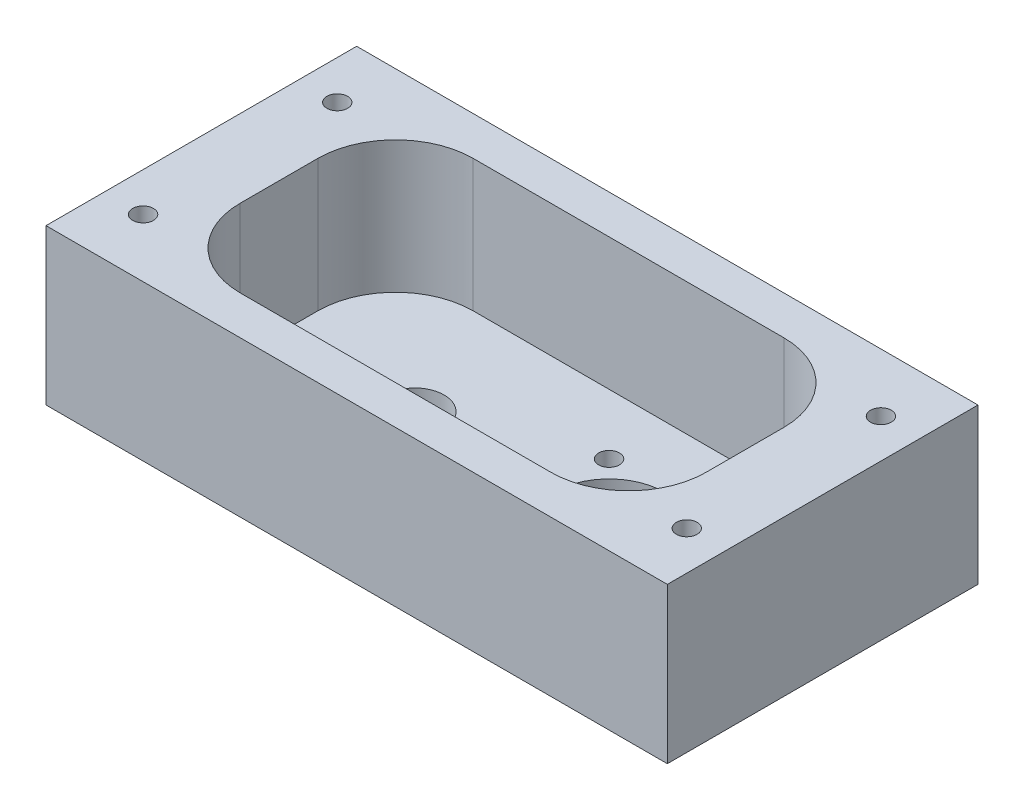
SolidWorks part; units mm, degrees
material "6061 Alloy"
ref_plane "Front Plane" through (0, 0, 0) normal (0, 0, 1) x (1, 0, 0)
ref_plane "Top Plane" through (0, 0, 0) normal (0, 1, 0) x (1, 0, 0)
ref_plane "Right Plane" through (0, 0, 0) normal (1, 0, 0) x (0, 0, -1)
sketch "Sketch1" plane through (0, 0, 0) normal (0, 1, 0) x (1, 0, 0)
  line L1 (-50.8, -25.4) -> (50.8, -25.4)
  line L2 (-50.8, -25.4) -> (-50.8, 25.4)
  line L3 (-50.8, 25.4) -> (50.8, 25.4)
  line L4 (50.8, -25.4) -> (50.8, 25.4)
  line L5 (-50.8, -25.4) -> (50.8, 25.4) construction
  line L6 (-50.8, 25.4) -> (50.8, -25.4) construction
  point P0 (0, 0)
  dimension "D1" = 101.6
  dimension "D2" = 50.8
extrude "Boss-Extrude1" add sketch "Sketch1" along normal blind 25.4
sketch "Sketch2" plane through (0, 0, 0) normal (0, -1, 0) x (1, 0, 0)
  line L0 (-50.8, 0) -> (50.8, 0) construction
  line L1 (-50.8, -25.4) -> (-50.8, 25.4) construction
  line L2 (50.8, 25.4) -> (50.8, -25.4) construction
  line L3 (0, 25.4) -> (0, -25.4) construction
  line L4 (-50.8, 25.4) -> (50.8, 25.4) construction
  line L5 (50.8, -25.4) -> (-50.8, -25.4) construction
  circle A0 centre (-15.875, 0) radius 4.7625
  circle A1 centre (15.875, 0) radius 9
  point P12 (-15.875, 0)
  point P13 (15.875, 0)
  dimension "D3" = 18
  dimension "D4" = 9.525
  dimension "D1" = 31.75
  dimension "D2" = 15.875
extrude "Cut-Extrude1" cut sketch "Sketch2" against normal through all contours A0 | A1
sketch "Sketch3" plane through (0, 25.4, 0) normal (0, 1, 0) x (1, 0, 0)
  line L0 (15.875, 0) -> (-15.875, 0) construction
  line L1 (-25.4, -19.05) -> (25.4, -19.05)
  line L2 (-38.1, -6.35) -> (-38.1, 6.35)
  line L3 (-25.4, 19.05) -> (25.4, 19.05)
  line L4 (38.1, -6.35) -> (38.1, 6.35)
  line L5 (-38.1, -19.05) -> (38.1, 19.05) construction
  line L6 (-38.1, 19.05) -> (38.1, -19.05) construction
  arc A0 (25.4, 19.05) -> (38.1, 6.35) centre (25.4, 6.35) cw
  arc A1 (38.1, -6.35) -> (25.4, -19.05) centre (25.4, -6.35) cw
  arc A2 (-25.4, -19.05) -> (-38.1, -6.35) centre (-25.4, -6.35) cw
  arc A3 (-38.1, 6.35) -> (-25.4, 19.05) centre (-25.4, 6.35) cw
  point P0 (0, 0)
  dimension "D3" = 12.7
  dimension "D1" = 38.1
  dimension "D2" = 76.2
extrude "Cut-Extrude2" cut sketch "Sketch3" against normal blind 21.59
sketch "Sketch4" plane through (0, 0, 0) normal (0, -1, 0) x (1, 0, 0)
  line L0 (-44.45, 25.4) -> (-44.45, -25.4) construction
  line L1 (-50.8, 25.4) -> (50.8, 25.4) construction
  line L2 (50.8, -25.4) -> (-50.8, -25.4) construction
  line L3 (44.45, 25.4) -> (44.45, -25.4) construction
  line L4 (-50.8, -25.4) -> (-50.8, 25.4) construction
  line L5 (50.8, 25.4) -> (50.8, -25.4) construction
  line L6 (-44.45, 0) -> (44.45, 0) construction
  line L7 (6.6826, 9.1924) -> (25.0674, -9.1924) construction
  line L8 (25.0674, 9.1924) -> (6.6826, -9.1924) construction
  circle A1 centre (15.875, 0) radius 9 construction
  point P12 (-44.45, 15.875)
  point P13 (-44.45, -15.875)
  point P14 (44.45, 15.875)
  point P15 (44.45, -15.875)
  point P20 (15.875, 0)
  point P25 (15.875, 0)
  point P27 (6.6826, 9.1924)
  point P28 (25.0674, 9.1924)
  point P29 (25.0674, -9.1924)
  point P30 (6.6826, -9.1924)
  dimension "D1" = 6.35
  dimension "D2" = 6.35
  dimension "D3" = 31.75
  dimension "D4" = 45
  dimension "D5" = 45
  dimension "D6" = 26
hole_wizard "M3 Clearance Hole1" positions "3DSketch1" profile "Sketch5" hole size "M3" standard "ANSI Metric" end condition through all
sketch3d "3DSketch1"
  point P0 (-44.45, 0, 15.875)
  point P3 (-44.45, 0, -15.875)
  point P6 (6.6826, 0, 9.1924)
  point P9 (6.6826, 0, -9.1924)
  point P12 (25.0674, 0, 9.1924)
  point P15 (25.0674, 0, -9.1924)
  point P18 (44.45, 0, 15.875)
  point P21 (44.45, 0, -15.875)
sketch "Sketch5" plane through (-44.45, 0, 15.875) normal (1, 0, 0) x (0, 0, -1)
  line L0 (0, 0) -> (0, 25.4)
  line L1 (0, 25.4) -> (1.7, 25.4)
  line L2 (1.7, 25.4) -> (1.7, 0)
  line L5 (1.7, 0) -> (0, 0)
  line L11 (0, -6.35) -> (0, 107.95) construction
  dimension "Thru Hole Dia." = 3.4
  dimension "Thru Hole Depth" = 25.4
equation "\"D2@Sketch4\"=\"D1@Sketch4\""
